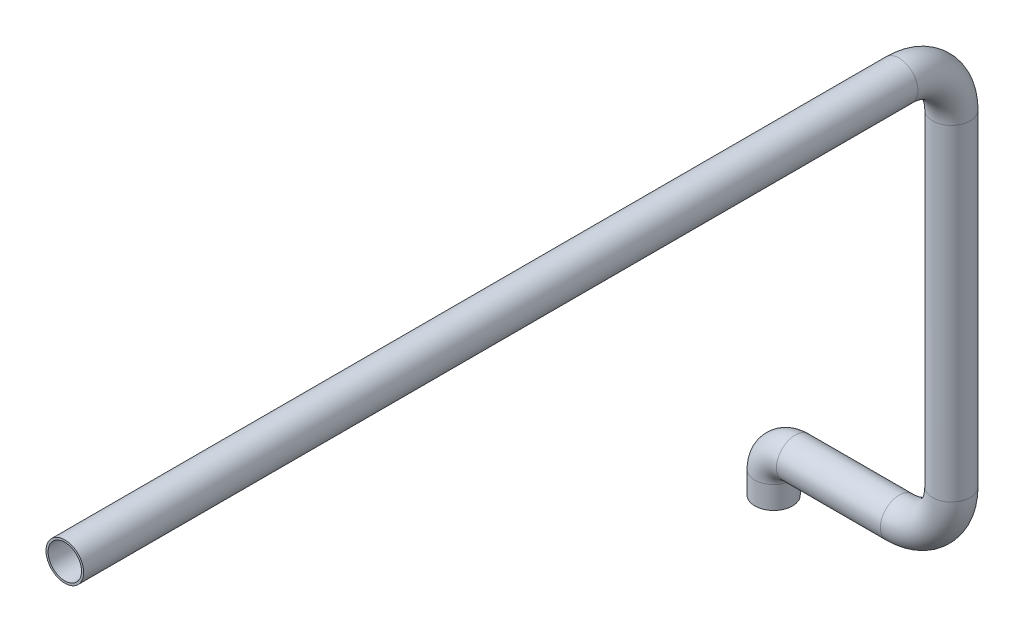
SolidWorks part; units mm, degrees
ref_plane "Front Plane" through (0, 0, 0) normal (0, 0, 1) x (1, 0, 0)
ref_plane "Top Plane" through (0, 0, 0) normal (0, 1, 0) x (1, 0, 0)
ref_plane "Right Plane" through (0, 0, 0) normal (1, 0, 0) x (0, 0, -1)
sketch "Sketch1" plane through (0, 0, 0) normal (0, 1, 0) x (1, 0, 0)
  circle A0 centre (0, 0) radius 9
  circle A1 centre (0, 0) radius 9
sketch3d "3DSketch1"
  line L0 (0, 0, 0) -> (0, 10.71, 0)
  line L1 (10.29, 21, 0) -> (60, 21, 0)
  line L2 (85, 46, 0) -> (85, 202, 0)
  line L3 (85, 227, 25) -> (85, 227, 424)
  arc A0 (0, 10.71, 0) -> (10.29, 21, 0) centre (10.29, 10.71, 0) cw
  arc A1 (60, 21, 0) -> (85, 46, 0) centre (60, 46, 0) cw
  arc A2 (85, 202, 0) -> (85, 227, 25) centre (85, 202, 25) cw
  point P4 (10.29, 10.71, -10.29)
  point P11 (60, 46, 25)
  point P18 (110, 202, 25)
sweep "Sweep1" add path "3DSketch1" circular profile diameter 18 parameters "D3"=18
sweep "Hollow_tube_OD_and_wall_PROVISIONAL" cut path "3DSketch1<2>" circular profile diameter 16 parameters "D3"=16
sketch3d "3DSketch1<2>" same geometry as "3DSketch1"
